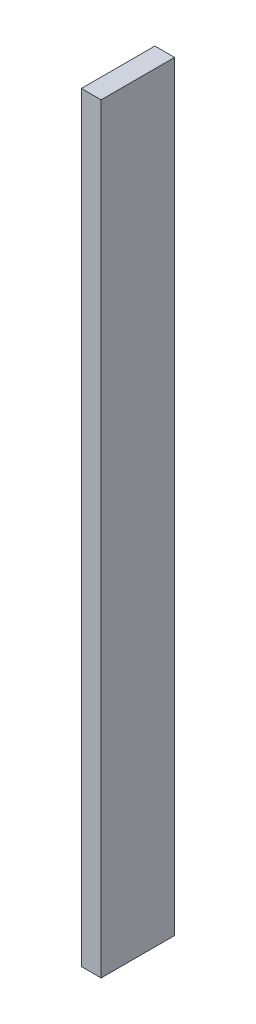
SolidWorks part; units mm, degrees
ref_plane "Front Plane" through (0, 0, 0) normal (0, 0, 1) x (1, 0, 0)
ref_plane "Top Plane" through (0, 0, 0) normal (0, 1, 0) x (1, 0, 0)
ref_plane "Right Plane" through (0, 0, 0) normal (1, 0, 0) x (0, 0, -1)
sketch "Sketch1" plane through (0, 0, 0) normal (1, 0, 0) x (0, 0, -1)
  line L1 (0, 0) -> (11.2, 0)
  line L2 (0, 0) -> (0, 115.857)
  line L3 (0, 115.857) -> (11.2, 115.857)
  line L4 (11.2, 0) -> (11.2, 115.857)
sketch "Sketch2" plane through (0, 0, 0) normal (0, 1, 0) x (1, 0, 0)
  line L1 (-3, 0) -> (0, 0)
  line L2 (-3, 0) -> (-3, 11.2)
  line L3 (-3, 11.2) -> (0, 11.2)
  line L4 (0, 0) -> (0, 11.2)
extrude "Boss-Extrude1" add sketch "Sketch1" against normal up to vertex (3 mm away) up to point (-3, 0, 0)
